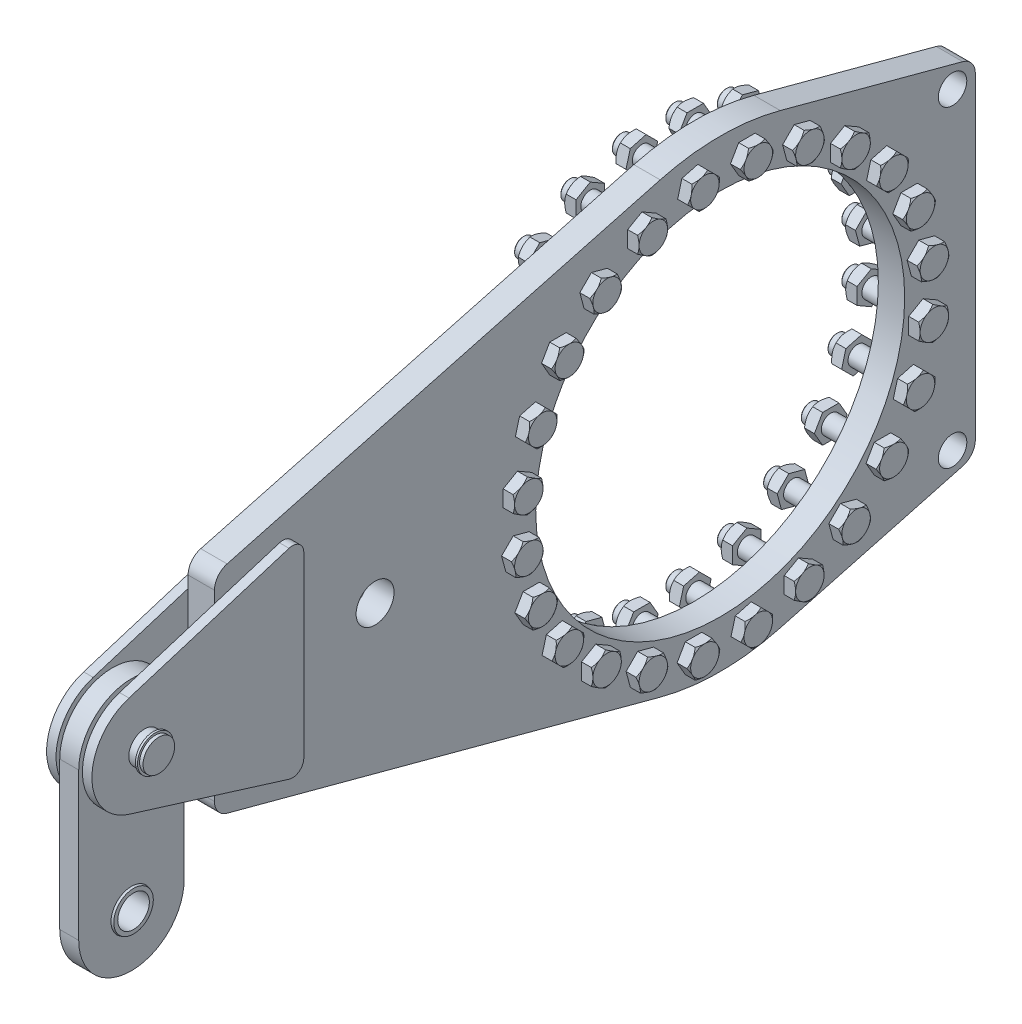
SolidWorks part; units mm, degrees
ref_plane "前视基准面" through (0, 0, 0) normal (0, 0, 1) x (1, 0, 0)
ref_plane "上视基准面" through (0, 0, 0) normal (0, 1, 0) x (1, 0, 0)
ref_plane "右视基准面" through (0, 0, 0) normal (1, 0, 0) x (0, 0, -1)
sketch "草图1" plane through (0, 0, 0) normal (1, 0, 0) x (0, 0, -1)
  line L0 (56.9402, 212.5037) -> (242, 162.9171)
  line L1 (242, 162.9171) -> (242, 0)
  line L2 (242, 0) -> (-479.75, 0) construction
  line L3 (0, 220) -> (0, -220) construction
  line L4 (-56.9402, 212.5037) -> (-479.75, 99.2121)
  line L5 (-479.75, 99.2121) -> (-479.75, 0)
  line L6 (-605, 0) -> (-605, -140)
  line L7 (-505, 0) -> (-505, -140)
  line L8 (-569.8193, 47.7534) -> (-404, 99.2121)
  line L9 (-404, 99.2121) -> (-404, -99.2121)
  line L10 (-569.8193, -47.7534) -> (-404, -99.2121)
  line L11 (0, 0) -> (242, 162.9171) construction
  line L12 (0, 0) -> (25.3221, 192.3403) construction
  line L13 (220.4, 148.3757) -> (242, 148.3757)
  circle A0 centre (0, 0) radius 194 construction
  circle A1 centre (0, 0) radius 175
  circle A2 centre (0, 0) radius 220
  arc A3 (-605, 0) -> (-505, 0) centre (-555, 0) cw
  arc A4 (-605, -140) -> (-505, -140) centre (-555, -140) ccw
  circle A5 centre (-555, 0) radius 15
  arc A6 (-605, 0) -> (-569.8193, -47.7534) centre (-555, 0) ccw
  circle A7 centre (220.4, 148.3757) radius 13.5
  circle A8 centre (-327.375, 0) radius 18
  circle A9 centre (25.3221, 192.3403) radius 9
  point P31 (0, -24)
  dimension "D1" = 30
  dimension "k" = 388
  dimension "d4" = 350
  dimension "D3" = 440
  dimension "D5" = 75
  dimension "D9" = 21.6
  dimension "s" = 18
  dimension "D10" = 27
  dimension "D11" = 36
  dimension "D2" = 484
  dimension "D6" = 479.75
  dimension "h" = 100
  dimension "f" = 140
  dimension "m" = 605
  dimension "D7" = 404
  dimension "D8" = 7.5
  dimension "n" = 24
  dimension "D12" = 327.375
sketch "草图2" plane through (0, 0, 0) normal (0, 0, 1) x (1, 0, 0)
  line L0 (-12.5, 220) -> (-12.5, -220)
  line L1 (-12.5, -220) -> (12.5, -220)
  line L2 (12.5, -220) -> (12.5, 220)
  line L3 (12.5, 220) -> (-12.5, 220)
  line L5 (0, 0) -> (165, 0) construction
  line L6 (0, 220) -> (0, -220) construction
  line L7 (0, -220) -> (0, 220) construction
  point P11 (21.5, 0)
  point P14 (-9, 0)
  point P15 (9, 0)
  point P16 (11, 0)
  point P17 (-11, 0)
  point P18 (-21.5, 0)
  point P19 (-35, 0)
  point P22 (35, 0)
  point P23 (29.75, 0)
  point P24 (-29.75, 0)
  point P25 (-36.5, 220)
  point P26 (-56.3, 220)
  dimension "D1" = 9
  dimension "G10" = 25
  dimension "G2" = 165
  dimension "c" = 18
  dimension "B" = 22
  dimension "D2" = 19.8
  dimension "j" = 70
  dimension "g" = 59.5
  dimension "(C)" = 24
ref_plane "基准面1" through (0, 0, 555) normal (0, 0, 1) x (1, 0, 0)
sketch "草图3" plane through (0, 0, 0) normal (1, 0, 0) x (0, 0, -1)
  line L0 (-56.9402, 212.5037) -> (-479.75, 99.2121) construction
  line L1 (-479.75, 99.2121) -> (-479.75, 0) construction
  line L2 (56.9402, 212.5037) -> (242, 162.9171) construction
  line L3 (242, 162.9171) -> (242, 0) construction
  line L4 (242, 0) -> (-479.75, 0) construction
  line L5 (-56.9402, 212.5037) -> (-479.75, 99.2121)
  line L6 (-479.75, 99.2121) -> (-479.75, -99.2121)
  line L7 (56.9402, 212.5037) -> (242, 162.9171)
  line L8 (242, 162.9171) -> (242, -162.9171)
  line L9 (242, 0) -> (-479.75, 0) construction
  line L10 (56.9402, -212.5037) -> (242, -162.9171)
  line L11 (-56.9402, -212.5037) -> (-479.75, -99.2121)
  circle A0 centre (0, 0) radius 220 construction
  arc A1 (56.9402, 212.5037) -> (-56.9402, 212.5037) centre (0, 0) ccw
  arc A2 (56.9402, -212.5037) -> (-56.9402, -212.5037) centre (0, 0) cw
  circle A3 centre (0, 0) radius 175 construction
  circle A4 centre (0, 0) radius 175
  circle A5 centre (220.4, 148.3757) radius 13.5 construction
  circle A6 centre (-327.375, 0) radius 18 construction
  circle A7 centre (220.4, 148.3757) radius 13.5
  circle A8 centre (-327.375, 0) radius 18
  circle A9 centre (220.4, -148.3757) radius 13.5
extrude "凸台-拉伸1" add sketch "草图3" along normal up to vertex (12.5 mm away) up to point (12.5, 220, 0)
sketch "草图5" plane through (0, 0, 0) normal (1, 0, 0) x (0, 0, -1)
  line L0 (-569.8193, -47.7534) -> (-404, -99.2121) construction
  line L1 (-569.8193, 47.7534) -> (-404, 99.2121) construction
  line L2 (-404, 99.2121) -> (-404, -99.2121) construction
  line L3 (-569.8193, -47.7534) -> (-404, -99.2121)
  line L4 (-569.8193, 47.7534) -> (-404, 99.2121)
  line L5 (-404, 99.2121) -> (-404, -99.2121)
  arc A0 (-605, 0) -> (-569.8193, -47.7534) centre (-555, 0) ccw construction
  arc A1 (-505, 0) -> (-605, 0) centre (-555, 0) ccw construction
  arc A2 (-605, 0) -> (-569.8193, -47.7534) centre (-555, 0) ccw
  arc A3 (-569.8193, 47.7534) -> (-605, 0) centre (-555, 0) ccw
  circle A4 centre (-555, 0) radius 15
  circle A5 centre (-555, 0) radius 15 construction
extrude "凸台-拉伸2" add sketch "草图5" against normal up to surface (-12.5 mm away) from vertex up to face at (12.5, 0, 309.375) starting at point (21.5, 0, 0)
fillet "圆角1" radius 10.8 2 edges at (17, -99.2121, 404) (17, 99.2121, 404)
mirror "镜向1" about plane through (0, 0, 0) normal (1, 0, 0) of "圆角1", "凸台-拉伸1", "凸台-拉伸2"
sketch "草图6" plane through (0, 0, 0) normal (1, 0, 0) x (0, 0, -1)
  circle A0 centre (25.3221, 192.3403) radius 9
  circle A1 centre (25.3221, 192.3403) radius 9 construction
extrude "切除-拉伸1" cut sketch "草图6" along normal up to vertex (12.5 mm away) from vertex up to point (12.5, 220, 0) starting at point (-12.5, 220, 0)
pattern_circular "阵列(圆周)1" count 24 over 360 about axis through (12.5, 0, 0) along (-1, 0, 0) of "切除-拉伸1"
sketch "草图7" plane through (0, 0, 0) normal (1, 0, 0) x (0, 0, -1)
  line L0 (-605, 0) -> (-605, -140) construction
  line L1 (-505, 0) -> (-505, -140) construction
  line L2 (-605, 0) -> (-605, -140)
  line L3 (-505, 0) -> (-505, -140)
  arc A0 (-505, 0) -> (-605, 0) centre (-555, 0) ccw construction
  arc A1 (-605, -140) -> (-505, -140) centre (-555, -140) ccw construction
  arc A2 (-505, 0) -> (-605, 0) centre (-555, 0) ccw
  arc A3 (-605, -140) -> (-505, -140) centre (-555, -140) ccw
  circle A4 centre (-555, 0) radius 15 construction
  circle A6 centre (-555, 0) radius 15
  circle A7 centre (-555, -140) radius 15
extrude "凸台-拉伸3" add sketch "草图7" along normal up to vertex (9 mm away) from vertex separate body up to point (9, 0, 0) starting at point (-9, 0, 0)
sketch "草图9" plane through (0, 0, 555) normal (0, 0, 1) x (1, 0, 0)
  line L0 (-11, 15) -> (-11, 18.75)
  line L1 (11, 18.75) -> (11, 15)
  line L2 (11, 0) -> (-11, 0) construction
  line L3 (0, 0) -> (0, 3.75) construction
  line L4 (0, 3.75) -> (0, 7.5) construction
  line L7 (0, 7.5) -> (0, 11.25) construction
  line L8 (0, 11.25) -> (0, 15) construction
  line L9 (0, 15) -> (0, 18.75) construction
  line L12 (0, 18.75) -> (0, 22.5) construction
  line L13 (-11, 15) -> (11, 15)
  arc A0 (-11, 18.75) -> (11, 18.75) centre (0, -12.5792) cw
  point P18 (0, 20.625)
revolve "旋转1" add sketch "草图9" angle 360 about L2
pattern_linear "阵列(线性)1" count 2 spacing 140 along (0, -1, 0) of "旋转1"
sketch "草图12" plane through (0, 0, 555) normal (0, 0, 1) x (1, 0, 0)
  line L0 (-35, 0) -> (-35, 15)
  line L1 (-35, 15) -> (-31.75, 15)
  line L2 (-31.75, 15) -> (-31.75, 17)
  line L3 (-31.75, 17) -> (-29.75, 17)
  line L5 (-29.75, 17) -> (-29.75, 15)
  line L6 (-29.75, 15) -> (29.75, 15)
  line L9 (-35, 0) -> (35, 0)
  line L10 (0, 0) -> (0, 15) construction
  line L11 (29.75, 17) -> (29.75, 15)
  line L12 (31.75, 17) -> (29.75, 17)
  line L13 (31.75, 15) -> (31.75, 17)
  line L14 (35, 15) -> (31.75, 15)
  line L15 (35, 0) -> (35, 15)
  dimension "D1" = 2
revolve "旋转2" add sketch "草图12" angle 360 about L9
sketch "草图14" plane through (12.5, 197.3571, 57.4561) normal (1, 0, 0) x (0, 0, -1)
  line L1 (67.1898, -5.0168) -> (74.984, -18.5168)
  line L2 (74.984, -18.5168) -> (90.5725, -18.5168)
  line L3 (90.5725, -18.5168) -> (98.3667, -5.0168)
  line L4 (98.3667, -5.0168) -> (90.5725, 8.4832)
  line L5 (90.5725, 8.4832) -> (74.984, 8.4832)
  line L6 (74.984, 8.4832) -> (67.1898, -5.0168)
  circle A0 centre (82.7782, -5.0168) radius 13.5 construction
  dimension "D1" = 27
extrude "拉伸-螺栓" add sketch "草图14" along normal blind 10.8
sketch "草图21" plane through (23.3, 192.3403, -25.3221) normal (1, 0, 0) x (0, 0, -1)
  line L0 (13.5, 0) -> (17.6769, 0) construction
  circle A0 centre (0, 0) radius 13.5 construction
  circle A1 centre (0, 0) radius 13.5
  circle A2 centre (0, 0) radius 17.6769
extrude "切除-螺栓" cut sketch "草图21" against normal up to vertex (10.8 mm away) draft 55 up to point (12.5, 192.3403, -40.9105)
sketch "草图22" plane through (0, 0, 0) normal (1, 0, 0) x (0, 0, -1)
  circle A0 centre (25.3221, 192.3403) radius 9 construction
  circle A1 centre (25.3221, 192.3403) radius 9
extrude "凸台-拉伸6" add sketch "草图22" against normal up to vertex (56.3 mm away) from vertex up to point (-56.3, 220, 0) starting at point (12.5, 220, 0)
chamfer "倒角1" distance 0.9 angle 45 1 edges at (-56.3, 192.3403, -34.3221)
sketch "草图23" plane through (0, 0, 0) normal (1, 0, 0) x (0, 0, -1)
  line L1 (40.9105, 192.3403) -> (33.1163, 205.8403)
  line L2 (33.1163, 205.8403) -> (17.5279, 205.8403)
  line L3 (17.5279, 205.8403) -> (9.7336, 192.3403)
  line L4 (9.7336, 192.3403) -> (17.5279, 178.8403)
  line L5 (17.5279, 178.8403) -> (33.1163, 178.8403)
  line L6 (33.1163, 178.8403) -> (40.9105, 192.3403)
  circle A0 centre (25.3221, 192.3403) radius 13.5 construction
  circle A1 centre (25.3221, 192.3403) radius 13.5 construction
extrude "凸台-拉伸7" add sketch "草图23" against normal blind 10.8 from vertex starting at point (-36.5, 220, 0)
sketch "草图24" plane through (-47.3, 0, 0) normal (-1, 0, 0) x (0, 0, 1)
  line L0 (-38.8221, 192.3403) -> (-42.999, 192.3403) construction
  circle A0 centre (-25.3221, 192.3403) radius 13.5
  circle A1 centre (-25.3221, 192.3403) radius 17.6769
  circle A3 centre (-25.3221, 192.3403) radius 13.5 construction
extrude "切除-拉伸3" cut sketch "草图24" against normal up to vertex (10.8 mm away) draft 55 up to point (-36.5, 205.8403, -33.1163)
pattern_circular "阵列(圆周)2" count 24 over 360 about axis through (12.5, 0, 0) along (-1, 0, 0) of "拉伸-螺栓", "切除-螺栓", "凸台-拉伸6", "倒角1", "凸台-拉伸7", "切除-拉伸3"
fillet "圆角2" radius 16.2 4 edges at (0, -162.9171, -242) (0, 162.9171, -242) (0, -99.2121, 479.75) (0, 99.2121, 479.75)
equation "\"D2@草图1\" = \"D3@草图1\" * 1.1"
equation "\"D6@草图1\" =  ( \"m@草图1\" - \"h@草图1\" )  * 0.95"
equation "\"D7@草图1\" = (  \"m@草图1\" - \"h@草图1\" )  * 0.8"
equation "\"D1@草图2\" = \"c@草图2\" / 2"
equation "\"D8@草图1\" = 180/\"n@草图1\""
equation "\"D1@阵列(圆周)1\" = \"n@草图1\""
equation "\"D3@阵列(线性)1\" = \"f@草图1\""
equation "\"D1@草图14\" = \"s@草图1\" * 1.5"
equation "\"D1@拉伸-螺栓\" = \"D1@草图14\"*0.4"
equation "\"D2@草图2\" = \"s@草图1\" * 1.1"
equation "\"D1@倒角1\" = \"s@草图1\" * 0.05"
equation "\"D1@凸台-拉伸7\" = \"D1@拉伸-螺栓\""
equation "\"D1@阵列(圆周)2\" = \"n@草图1\""
equation "\"D9@草图1\" = \"s@草图1\" * 1.2"
equation "\"D10@草图1\" = \"s@草图1\" * 1.5"
equation "\"D11@草图1\" = \"s@草图1\" * 2"
equation "\"D12@草图1\" =  ( \"d4@草图1\" / 2 +\"D6@草图1\" )  / 2"
equation "\"D1@圆角2\" = \"D10@草图1\" * 0.6"
equation "\"D1@圆角1\" = \"s@草图1\" * 0.6"
